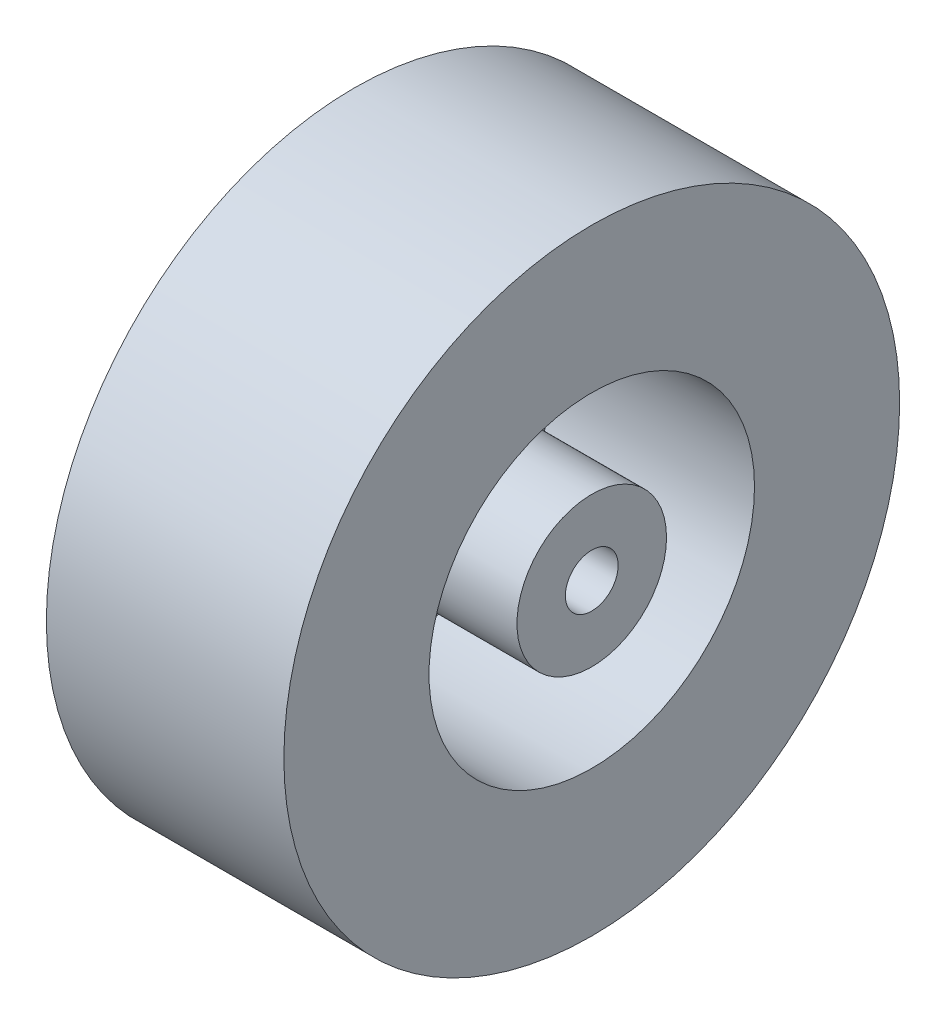
SolidWorks part; units mm, degrees
ref_plane "Front Plane" through (0, 0, 0) normal (0, 0, 1) x (1, 0, 0)
ref_plane "Top Plane" through (0, 0, 0) normal (0, 1, 0) x (1, 0, 0)
ref_plane "Right Plane" through (0, 0, 0) normal (1, 0, 0) x (0, 0, -1)
sketch "Sketch1" plane through (0, 0, 0) normal (1, 0, 0) x (0, 0, -1)
  circle A0 centre (0, 0) radius 35
extrude "Boss-Extrude1" add sketch "Sketch1" along normal blind 27
sketch "Sketch2" plane through (0, 0, 0) normal (-1, 0, 0) x (0, 0, 1)
  circle A0 centre (0, 0) radius 3
extrude "Cut-Extrude1" cut sketch "Sketch2" against normal up to next
sketch "Sketch3" plane through (27, 0, 0) normal (1, 0, 0) x (0, 0, -1)
  circle A0 centre (0, 0) radius 8.5
  circle A1 centre (0, 0) radius 18.5
extrude "Cut-Extrude2" cut sketch "Sketch3" against normal blind 23
sketch "Sketch4" plane through (27, 0, 0) normal (1, 0, 0) x (0, 0, -1)
  circle A0 centre (0, 0) radius 23.5
